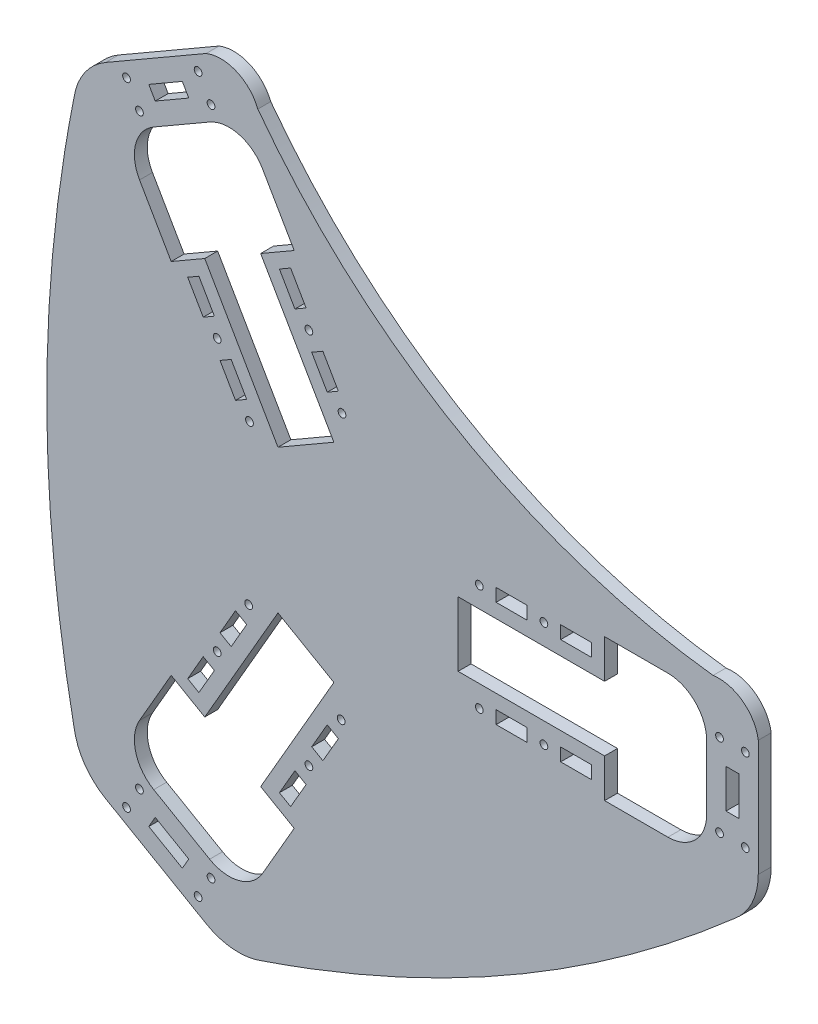
SolidWorks part; units mm, degrees
ref_plane "Front Plane" through (0, 0, 0) normal (0, 0, 1) x (1, 0, 0)
ref_plane "Top Plane" through (0, 0, 0) normal (0, 1, 0) x (1, 0, 0)
ref_plane "Right Plane" through (0, 0, 0) normal (1, 0, 0) x (0, 0, -1)
sketch "Sketch1" plane through (0, 0, 0) normal (0, 0, 1) x (1, 0, 0)
  line L0 (-8.8184, -40.2739) -> (-43.8184, -100.8957)
  line L1 (39.2875, -12.5) -> (109.2875, -12.5)
  line L2 (39.2875, -12.5) -> (39.2875, 12.5)
  line L3 (39.2875, 12.5) -> (109.2875, 12.5)
  line L4 (39.2875, 0) -> (0, 0) construction
  line L5 (39.2875, -12.5) -> (109.2875, 12.5) construction
  line L6 (39.2875, 12.5) -> (109.2875, -12.5) construction
  line L7 (-30.4691, -27.7739) -> (-8.8184, -40.2739)
  line L8 (-30.4691, -27.7739) -> (-65.4691, -88.3957)
  line L9 (-30.4691, 27.7739) -> (-65.4691, 88.3957)
  line L10 (-8.8184, 40.2739) -> (-30.4691, 27.7739)
  line L11 (-8.8184, 40.2739) -> (-43.8184, 100.8957)
  arc A0 (-43.8184, -100.8957) -> (109.2875, -12.5) centre (0, 0) ccw
  arc A1 (-65.4691, 88.3957) -> (-65.4691, -88.3957) centre (0, 0) ccw
  arc A2 (109.2875, 12.5) -> (-43.8184, 100.8957) centre (0, 0) ccw
  point P4 (74.2875, 0)
  dimension "D4" = 110
  dimension "D1" = 70
  dimension "D2" = 25
  dimension "D3" = 3
extrude "Boss-Extrude1" add sketch "Sketch1" along normal blind 5
sketch "Sketch3" plane through (0, 0, 5) normal (0, 0, 1) x (1, 0, 0)
  line L0 (145.507, -22.5) -> (145.507, 22.5)
  line L1 (130.507, 37.5) -> (96.507, 37.5)
  line L2 (96.507, -37.5) -> (96.507, 37.5)
  line L3 (130.507, -37.5) -> (96.507, -37.5)
  line L4 (145.507, -37.5) -> (145.507, 37.5) construction
  line L5 (145.507, -37.5) -> (96.507, -37.5) construction
  line L6 (145.507, 37.5) -> (96.507, 37.5) construction
  line L7 (120.507, -27.5) -> (106.507, -27.5)
  line L8 (135.507, -12.5) -> (135.507, 12.5)
  line L9 (120.507, 27.5) -> (106.507, 27.5)
  line L10 (106.507, -27.5) -> (106.507, 27.5)
  line L11 (135.507, -27.5) -> (106.507, 27.5) construction
  line L12 (135.507, 27.5) -> (106.507, -27.5) construction
  line L13 (135.507, -27.5) -> (135.507, 27.5) construction
  line L14 (135.507, -27.5) -> (106.507, -27.5) construction
  line L15 (135.507, 27.5) -> (106.507, 27.5) construction
  arc A1 (-43.8184, -100.8957) -> (109.2875, -12.5) centre (0, 0) ccw construction
  arc A2 (145.507, -22.5) -> (130.507, -37.5) centre (130.507, -22.5) cw
  arc A3 (145.507, 22.5) -> (130.507, 37.5) centre (130.507, 22.5) ccw
  arc A4 (135.507, -12.5) -> (120.507, -27.5) centre (120.507, -12.5) cw
  arc A5 (135.507, 12.5) -> (120.507, 27.5) centre (120.507, 12.5) ccw
  point P0 (121.007, 0)
  point P8 (121.007, 0)
  dimension "D4" = 15
  dimension "D1" = 29
  dimension "D2" = 55
  dimension "D3" = 10
extrude "Boss-Extrude2" add sketch "Sketch3" against normal blind 5
sketch "Sketch4" plane through (0, 0, 5) normal (0, 0, 1) x (1, 0, 0)
  line L0 (106.507, 12.5) -> (106.507, -12.5) construction
  line L1 (117.0141, -27.5) -> (96, -27.5)
  line L2 (117.0141, -27.5) -> (117.0141, 27.5)
  line L3 (117.0141, 27.5) -> (96, 27.5)
  line L4 (96, -27.5) -> (96, 27.5)
  line L5 (117.0141, -27.5) -> (96, 27.5) construction
  line L6 (117.0141, 27.5) -> (96, -27.5) construction
  line L7 (120.507, 27.5) -> (106.507, 27.5) construction
  line L8 (54, 20.5) -> (47.5, 20.5) construction
  line L9 (91, -18) -> (91, -23) construction
  line L10 (79, -20.5) -> (66, -20.5) construction
  line L11 (91, -18) -> (79, -18)
  line L12 (91, -18) -> (91, -23)
  line L13 (91, -23) -> (79, -23)
  line L14 (79, -18) -> (79, -23)
  line L15 (66, -18) -> (54, -18)
  line L16 (66, -18) -> (66, -23)
  line L17 (66, -23) -> (54, -23)
  line L18 (54, -18) -> (54, -23)
  line L19 (91, 23) -> (79, 23)
  line L20 (91, 23) -> (91, 18)
  line L21 (91, 18) -> (79, 18)
  line L22 (79, 23) -> (79, 18)
  line L23 (66, 23) -> (54, 23)
  line L24 (66, 23) -> (66, 18)
  line L25 (66, 18) -> (54, 18)
  line L26 (54, 23) -> (54, 18)
  line L27 (79, 20.5) -> (66, 20.5) construction
  line L28 (54, -20.5) -> (47.5, -20.8619) construction
  circle A0 centre (72.5, -20.5) radius 1.5
  circle A1 centre (72.5, 20.5) radius 1.5
  circle A2 centre (47.5, 20.5) radius 1.5
  circle A3 centre (47.5, -20.8619) radius 1.5
  point P0 (106.507, 0)
  dimension "D2" = 3
  dimension "D4" = 3
  dimension "D1" = 5
  dimension "D3" = 6.5
extrude "Cut-Extrude1" cut sketch "Sketch4" against normal blind 5
pattern_circular "CirPattern1" count 3 over 360 about axis through (0, 0, 5) along (0, 0, 1) of "Cut-Extrude1", "Boss-Extrude2"
sketch "Sketch5" plane through (0, 0, 5) normal (0, 0, 1) x (1, 0, 0)
  circle A0 centre (130.507, 226.0448) radius 188.5448
  arc A1 (130.507, 37.5) -> (-32.7776, 131.7724) centre (98.5082, 170.6211) cw
extrude "Cut-Extrude2" cut sketch "Sketch5" against normal blind 5 contours A0
extrude "Boss-Extrude3" add sketch "Sketch5<2>" against normal blind 5 contours A0 | A0 region at (35.2823, 61.1107, 5)
sketch "Sketch5<2>" plane through (0, 0, 5) normal (0, 0, 1) x (1, 0, 0) same geometry as "Sketch5"
sketch "Sketch6" plane through (0, 0, 5) normal (0, 0, 1) x (1, 0, 0)
  line L0 (0, 0) -> (-19.6437, -34.0239) construction
  line L1 (-30.4691, -27.7739) -> (-8.8184, -40.2739) construction
  arc A0 (130.507, -37.5) -> (145.507, -22.5) centre (130.507, -22.5) ccw construction
  arc A1 (-19.2293, -108.3062) -> (103.4106, -37.5) centre (0, 0) ccw construction
  arc A2 (-53.2679, -137.2628) -> (-32.7776, -131.7724) centre (-45.7679, -124.2724) ccw construction
  arc A5 (141.1136, -33.1066) -> (-41.8857, -138.7613) centre (102.4413, -177.4336) ccw
  arc A8 (-99.228, 105.6547) -> (-99.228, -105.6547) centre (-204.8827, 0) cw
  spline S0 degree 2 poles (141.1136, -33.1066) (60.386, -104.5916) (-41.8857, -138.7613) knots 0 0 0 1 1 1
  spline S1 degree 2 poles (-99.228, 105.6547) (-120.772, 0) (-99.228, -105.6547) knots 0 0 0 1 1 1
extrude "Boss-Extrude4" add sketch "Sketch6" against normal blind 5 contours S0 A5 | A8 S1 region at (42.8622, -74.2396, 5) region at (-85.7245, 0, 5)
sketch "Sketch7" plane through (0, 0, 0) normal (0, 0, -1) x (-1, 0, 0)
  line L0 (38.2679, 137.2628) -> (-138.007, 35.4904) construction
  line L1 (48.7679, 119.0763) -> (-127.507, 17.3038) construction
  line L19 (-155.507, -22.5) -> (-155.507, 22.5)
  line L20 (97.2391, -123.423) -> (58.2679, -145.923)
  line L21 (58.2679, 145.923) -> (97.2391, 123.423)
  line L22 (-155.507, -22.5) -> (-155.507, 22.5)
  line L23 (97.2391, -123.423) -> (58.2679, -145.923)
  line L24 (58.2679, 145.923) -> (97.2391, 123.423)
  line L46 (-145.507, 22.5) -> (-145.507, -22.5)
  line L47 (53.2679, -137.2628) -> (92.2391, -114.7628)
  line L48 (92.2391, 114.7628) -> (53.2679, 137.2628)
  line L49 (-145.507, 22.5) -> (-145.507, -22.5)
  line L50 (53.2679, -137.2628) -> (92.2391, -114.7628)
  line L51 (92.2391, 114.7628) -> (53.2679, 137.2628)
  arc A0 (53.2679, 137.2628) -> (32.7776, 131.7724) centre (45.7679, 124.2724) ccw construction
  arc A1 (-130.507, 37.5) -> (-145.507, 22.5) centre (-130.507, 22.5) ccw construction
  arc A2 (38.2679, 137.2628) -> (-138.007, 35.4904) centre (-167.9246, 290.8539) cw
  arc A22 (38.2679, 137.2628) -> (58.2679, 145.923) centre (52.5981, 131.5929) cw
  arc A23 (-155.507, 22.5) -> (-138.007, 35.4904) centre (-140.2619, 20.2452) cw
  arc A24 (-155.507, 22.5) -> (-138.007, 35.4904) centre (-140.2619, 20.2452) cw
  arc A26 (-155.507, -22.5) -> (-146.1163, -42.0282) centre (-130.507, -22.5) ccw
  arc A27 (36.6607, -147.5545) -> (58.2679, -145.923) centre (45.7679, -124.2724) ccw
  arc A28 (97.2391, -123.423) -> (109.4556, -105.5264) centre (84.7391, -101.7724) ccw
  arc A29 (109.4556, 105.5264) -> (97.2391, 123.423) centre (84.7391, 101.7724) ccw
  arc A30 (-155.507, -22.5) -> (-146.1163, -42.0282) centre (-130.507, -22.5) ccw
  arc A31 (36.6607, -147.5545) -> (58.2679, -145.923) centre (45.7679, -124.2724) ccw
  arc A32 (97.2391, -123.423) -> (109.4556, -105.5264) centre (84.7391, -101.7724) ccw
  arc A33 (109.4556, 105.5264) -> (97.2391, 123.423) centre (84.7391, 101.7724) ccw
  arc A83 (-130.507, 37.5) -> (32.7776, 131.7724) centre (-130.507, 226.0448) ccw
  arc A84 (-130.507, 37.5) -> (-145.507, 22.5) centre (-130.507, 22.5) ccw
  arc A85 (-145.507, -22.5) -> (-139.7122, -34.3434) centre (-130.507, -22.5) ccw
  arc A86 (40.1139, -138.166) -> (53.2679, -137.2628) centre (45.7679, -124.2724) ccw
  arc A87 (92.2391, -114.7628) -> (99.5983, -103.8226) centre (84.7391, -101.7724) ccw
  arc A88 (99.5983, 103.8226) -> (92.2391, 114.7628) centre (84.7391, 101.7724) ccw
  arc A89 (53.2679, 137.2628) -> (32.7776, 131.7724) centre (45.7679, 124.2724) ccw
  arc A90 (-130.507, 37.5) -> (32.7776, 131.7724) centre (-130.507, 226.0448) ccw
  arc A91 (-130.507, 37.5) -> (-145.507, 22.5) centre (-130.507, 22.5) ccw
  arc A92 (-145.507, -22.5) -> (-139.7122, -34.3434) centre (-130.507, -22.5) ccw
  arc A93 (40.1139, -138.166) -> (53.2679, -137.2628) centre (45.7679, -124.2724) ccw
  arc A94 (92.2391, -114.7628) -> (99.5983, -103.8226) centre (84.7391, -101.7724) ccw
  arc A95 (99.5983, 103.8226) -> (92.2391, 114.7628) centre (84.7391, 101.7724) ccw
  arc A96 (53.2679, 137.2628) -> (32.7776, 131.7724) centre (45.7679, 124.2724) ccw
  parabola Q28 (-139.7122, -34.3434) -> (40.1139, -138.166) focus (74.536, 129.1001) apex (-55, -95.2628)
  parabola Q29 (99.5983, -103.8226) -> (99.5983, 103.8226) focus (-149.072, 0) apex (110, 0)
  parabola Q30 (-139.7122, -34.3434) -> (40.1139, -138.166) focus (74.536, 129.1001) apex (-55, -95.2628)
  parabola Q31 (99.5983, -103.8226) -> (99.5983, 103.8226) focus (-149.072, 0) apex (110, 0)
  spline S0 degree 3 poles (2538.0231, 1360.7126) (1333.5912, 96.4804) (419.2881, -380.6402) (-539.2786, 172.7886) (-583.2393, 1203.1233) (-90.6291, 2878.2494) knots -7.363878 -7.363878 -7.363878 -7.363878 0.5 0.5 8.363722 8.363722 8.363722 8.363722 only from (36.6607, -147.5545) to (-146.1163, -42.0282)
  spline S1 degree 3 poles (-2447.4232, 1517.6362) (-750.3501, 1106.6836) (120, 553.4342) (120, -553.4233) (-750.3157, -1106.6617) (-2447.3225, -1517.6118) knots -7.363878 -7.363878 -7.363878 -7.363878 0.5 0.5 8.363722 8.363722 8.363722 8.363722 only from (109.4556, 105.5264) to (109.4556, -105.5264)
  spline S2 degree 3 poles (36.6607, -147.5545) (2.7067, -136.0639) (-29.526, -121.5172) (-90.474, -86.3289) (-119.1881, -65.6879) (-146.1163, -42.0282) knots 0 0 0 0 0.5 0.5 1 1 1 1
  spline S3 degree 3 poles (109.4556, 105.5264) (116.4815, 70.376) (120, 35.1884) (120, -35.1884) (116.4815, -70.376) (109.4556, -105.5264) knots 0 0 0 0 0.5 0.5 1 1 1 1
  dimension "D1" = 21
  dimension "D2" = 10
  dimension "D3" = 0
  dimension "D4" = 0
extrude "Boss-Extrude5" add sketch "Sketch7" against normal blind 5 contours S3 A33 L24 A22 A96 L51 A95 Q31 A94 L50 A93 Q30 A92 L49 A91 A23 L22 A30 S2 A31 L23 A32 | A2 A90 region at (151.4613, 0, 0) region at (38.4894, 66.6656, 0)
extrude "Cut-Extrude3" cut sketch "Sketch7<3>" against normal blind 5 contours A2 A96 A90 | A90 A91 A2 region at (131.6458, 36.7807, 0) region at (-33.9699, 132.399, 0)
sketch "Sketch7<3>" plane through (0, 0, 0) normal (0, 0, -1) x (-1, 0, 0) same geometry as "Sketch7"
sketch "Sketch8" plane through (0, 0, 0) normal (0, 0, -1) x (-1, 0, 0)
  line L0 (-155.507, 0) -> (-135.507, 0) construction
  line L1 (-148.007, 7.5) -> (-143.007, 7.5)
  line L2 (-148.007, 7.5) -> (-148.007, -7.5)
  line L3 (-148.007, -7.5) -> (-143.007, -7.5)
  line L4 (-143.007, 7.5) -> (-143.007, -7.5)
  line L5 (-148.007, 7.5) -> (-143.007, -7.5) construction
  line L6 (-148.007, -7.5) -> (-143.007, 7.5) construction
  line L7 (-155.507, -22.5) -> (-155.507, 22.5) construction
  line L8 (-135.507, -12.5) -> (-135.507, 12.5) construction
  line L9 (-156.507, 16) -> (-134.507, 16) construction
  line L10 (-134.507, 16) -> (-134.507, -16) construction
  line L11 (-156.507, -16) -> (-134.507, -16) construction
  line L12 (-156.507, 16) -> (-156.507, -16) construction
  line L13 (-137.007, 13.5) -> (-137.007, -13.5) construction
  line L14 (-154.007, -13.5) -> (-137.007, -13.5) construction
  line L15 (-154.007, 13.5) -> (-154.007, -13.5) construction
  line L16 (-154.007, 13.5) -> (-137.007, 13.5) construction
  circle A0 centre (-140.507, 16) radius 1.5
  circle A1 centre (-140.507, -16) radius 1.5
  circle A2 centre (-150.507, -16) radius 1.5
  circle A3 centre (-150.507, 16) radius 1.5
  point P0 (-145.507, 0)
  dimension "D5" = 3
  dimension "D1" = 5
  dimension "D2" = 15
  dimension "D3" = 8.5
  dimension "D4" = 2.5
extrude "Cut-Extrude4" cut sketch "Sketch8" against normal blind 10
ref_axis "Axis1" through (0, 0, 0) along (0, 0, -1)
pattern_circular "CirPattern2" count 3 over 360 about axis through (0, 0, 0) along (0, 0, -1) of "Cut-Extrude4"
sketch "Sketch9" plane through (0, 0, 0) normal (0, 0, -1) x (-1, 0, 0)
  line L3 (-135.507, 15.6465) -> (-135.507, -22.5)
  line L4 (-135.507, 15.6465) -> (-135.507, -22.5)
  line L5 (48.2679, -128.6025) -> (87.2391, -106.1025)
  line L6 (48.2679, -128.6025) -> (87.2391, -106.1025)
  line L7 (87.2391, 106.1025) -> (54.2032, 125.1758)
  line L8 (87.2391, 106.1025) -> (54.2032, 125.1758)
  arc A7 (-135.507, 15.6465) -> (54.2032, 125.1758) centre (-167.9246, 290.8539) ccw
  arc A8 (-135.507, 15.6465) -> (54.2032, 125.1758) centre (-167.9246, 290.8539) ccw
  arc A9 (-135.507, -22.5) -> (-133.399, -26.5788) centre (-130.507, -22.5) ccw
  arc A10 (-135.507, -22.5) -> (-133.399, -26.5788) centre (-130.507, -22.5) ccw
  arc A11 (43.6816, -128.8163) -> (48.2679, -128.6025) centre (45.7679, -124.2724) ccw
  arc A12 (43.6816, -128.8163) -> (48.2679, -128.6025) centre (45.7679, -124.2724) ccw
  arc A13 (87.2391, -106.1025) -> (89.7174, -102.2375) centre (84.7391, -101.7724) ccw
  arc A14 (87.2391, -106.1025) -> (89.7174, -102.2375) centre (84.7391, -101.7724) ccw
  arc A15 (89.7174, 102.2375) -> (87.2391, 106.1025) centre (84.7391, 101.7724) ccw
  arc A16 (89.7174, 102.2375) -> (87.2391, 106.1025) centre (84.7391, 101.7724) ccw
  spline S0 degree 3 poles (-2338.9836, -2023.619) (-324.1449, 255.999) (-254.2768, 77.2878) (-126.911, -32.2069) (-122.0031, -36.3751) (-117.0228, -40.4516) (-106.9645, -48.4813) (-100.1287, -53.6697) (-89.6753, -61.2001) (-86.1574, -63.6681) (-79.0675, -68.5105) (-75.4938, -70.8861) (-64.6863, -77.8752) (-57.3661, -82.3513) (-46.2119, -88.7888) (-42.4625, -90.8898) (-34.9193, -94.9919) (-31.1257, -96.9931) (-19.6796, -102.848) (-4.2437, -110.2585) (11.5351, -116.8903) (23.4957, -121.5767) (29.5076, -123.8482) (35.5666, -126.0127) (194.3011, -181.646) (387.4888, -153.7223) (-690.1871, -3012.1307) knots -2.382424 -2.382424 -2.382424 -2.382424 0.03125 0.03125 0.0625 0.125 0.125 0.25 0.25 0.3125 0.3125 0.375 0.375 0.5 0.5 0.5625 0.5625 0.625 0.625 0.75 0.875 0.875 0.9375 0.96875 0.96875 3.387262 3.387262 3.387262 3.387262 only from (-133.399, -26.5788) to (43.6816, -128.8163)
  spline S1 degree 3 poles (-133.399, -26.5788) (-131.7854, -27.9965) (-130.1668, -29.4079) (-126.911, -32.2069) (-122.0031, -36.3751) (-117.0228, -40.4516) (-106.9645, -48.4813) (-100.1287, -53.6697) (-89.6753, -61.2001) (-86.1574, -63.6681) (-79.0675, -68.5105) (-75.4938, -70.8861) (-64.6863, -77.8752) (-57.3661, -82.3513) (-46.2119, -88.7888) (-42.4625, -90.8898) (-34.9193, -94.9919) (-31.1257, -96.9931) (-19.6796, -102.848) (-4.2437, -110.2585) (11.5351, -116.8903) (23.4957, -121.5767) (29.5076, -123.8482) (35.5666, -126.0127) (39.6164, -127.432) (41.6473, -128.1279) (43.6816, -128.8163) knots 0 0 0 0 0.03125 0.03125 0.0625 0.125 0.125 0.25 0.25 0.3125 0.3125 0.375 0.375 0.5 0.5 0.5625 0.5625 0.625 0.625 0.75 0.875 0.875 0.9375 0.96875 0.96875 1 1 1 1
  spline S2 degree 3 poles (2921.9972, -1013.8097) (-59.6292, -408.7173) (60.2052, -258.854) (91.3475, -93.8047) (92.5033, -87.4703) (93.5435, -81.1189) (95.4682, -68.3933) (96.5437, -59.8791) (97.8385, -47.061) (98.2169, -42.7805) (98.8656, -34.2192) (99.136, -29.9365) (99.785, -17.0824) (100.0014, -8.5048) (99.9993, 4.3738) (99.9441, 8.6713) (99.7251, 17.255) (99.5613, 21.5409) (98.9087, 34.381) (97.6085, 51.4541) (95.4624, 68.4348) (93.5407, 81.1362) (92.5018, 87.4784) (91.3469, 93.8079) (60.1595, 259.0927) (-60.617, 412.4363) (2953.6753, 908.3458) knots -2.382424 -2.382424 -2.382424 -2.382424 0.03125 0.03125 0.0625 0.125 0.125 0.25 0.25 0.3125 0.3125 0.375 0.375 0.5 0.5 0.5625 0.5625 0.625 0.625 0.75 0.875 0.875 0.9375 0.96875 0.96875 3.387262 3.387262 3.387262 3.387262 only from (89.7174, -102.2375) to (89.7174, 102.2375)
  spline S3 degree 3 poles (89.7174, -102.2375) (90.1384, -100.1313) (90.5514, -98.0239) (91.3475, -93.8047) (92.5033, -87.4703) (93.5435, -81.1189) (95.4682, -68.3933) (96.5437, -59.8791) (97.8385, -47.061) (98.2169, -42.7805) (98.8656, -34.2192) (99.136, -29.9365) (99.785, -17.0824) (100.0014, -8.5048) (99.9993, 4.3738) (99.9441, 8.6713) (99.7251, 17.255) (99.5613, 21.5409) (98.9087, 34.381) (97.6085, 51.4541) (95.4624, 68.4348) (93.5407, 81.1362) (92.5018, 87.4784) (91.3469, 93.8079) (90.5512, 98.0248) (90.1383, 100.1316) (89.7174, 102.2375) knots 0 0 0 0 0.03125 0.03125 0.0625 0.125 0.125 0.25 0.25 0.3125 0.3125 0.375 0.375 0.5 0.5 0.5625 0.5625 0.625 0.625 0.75 0.875 0.875 0.9375 0.96875 0.96875 1 1 1 1
  dimension "D1" = 20
extrude "Cut-Extrude5" [suppressed] cut sketch "Sketch9" against normal blind 10
sketch "Sketch10" [suppressed] plane through (0, 0, 0) normal (0, 0, -1) x (-1, 0, 0)
  line L0 (46.4744, 145.7351) -> (-149.4474, 32.6196)
  arc A0 (58.2679, 145.923) -> (38.2679, 137.2628) centre (52.5981, 131.5929) ccw construction
  arc A1 (-138.007, 35.4904) -> (-155.507, 22.5) centre (-140.2619, 20.2452) ccw construction
  arc A2 (46.4744, 145.7351) -> (-149.4474, 32.6196) centre (-97.8765, 169.527) cw
extrude "Boss-Extrude6" [suppressed] add sketch "Sketch10" against normal blind 5
sketch "Sketch11" [suppressed] plane through (0, 0, 0) normal (0, 0, -1) x (-1, 0, 0)
  line L0 (77.7535, -134.673) -> (0, 0) construction
  line L1 (97.2391, -123.423) -> (58.2679, -145.923) construction
  line L2 (0, 0) -> (-155.507, 0) construction
  line L3 (-155.507, -22.5) -> (-155.507, 22.5) construction
  line L4 (77.7535, 134.673) -> (0, 0) construction
  line L5 (58.2679, 145.923) -> (97.2391, 123.423) construction
  line L6 (-77.7535, 134.673) -> (0, 0) construction
  line L7 (-77.7535, -134.673) -> (0, 0) construction
  line L8 (0, 0) -> (155.507, 0) construction
  line L9 (0, -5) -> (155.507, -5)
  line L10 (-82.0836, 132.173) -> (-4.3301, -2.5)
  line L11 (-73.4234, -137.173) -> (4.3301, -2.5)
  line L12 (0, 5) -> (155.507, 5)
  line L13 (-73.4234, 137.173) -> (4.3301, 2.5)
  line L14 (-82.0836, -132.173) -> (-4.3301, 2.5)
  circle A0 centre (-239.9526, 0) radius 202.8051
  circle A1 centre (119.9763, 207.8051) radius 202.8051
  circle A2 centre (119.9763, -207.8051) radius 202.8051
  spline S2 degree 3 poles (109.4556, 105.5264) (116.4815, 70.376) (120, 35.1884) (120, -35.1884) (116.4815, -70.376) (109.4556, -105.5264) knots 0 0 0 0 0.5 0.5 1 1 1 1 construction
  spline S3 degree 3 poles (36.6607, -147.5545) (2.7067, -136.0639) (-29.526, -121.5172) (-90.474, -86.3289) (-119.1881, -65.6879) (-146.1163, -42.0282) knots 0 0 0 0 0.5 0.5 1 1 1 1 construction
  point P27 (119.9763, 5)
  point P30 (119.9763, -5)
  point P33 (-64.3183, -101.4025)
  dimension "D2" = 5
  dimension "D3" = 5
  dimension "D1" = 2
extrude "Boss-Extrude7" [suppressed] add sketch "Sketch11" against normal blind 5
sketch "Sketch12" [suppressed] plane through (0, 0, 0) normal (0, 0, -1) x (-1, 0, 0)
  circle A0 centre (16.8661, 113.4471) radius 1.98
  circle A1 centre (16.8661, 113.4471) radius 1.98 construction
  circle A2 centre (-119.5156, 34.7071) radius 1.98
  circle A3 centre (-42.0456, -99.4749) radius 1.98
  circle A4 centre (82.9061, -0.9376) radius 1.98
  circle A5 centre (82.9061, -0.9376) radius 1.98 construction
  circle A6 centre (-42.0456, -99.4749) radius 1.98 construction
  circle A7 centre (-119.5156, 34.7071) radius 1.98 construction
extrude "Cut-Extrude6" [suppressed] cut sketch "Sketch12" against normal blind 5
